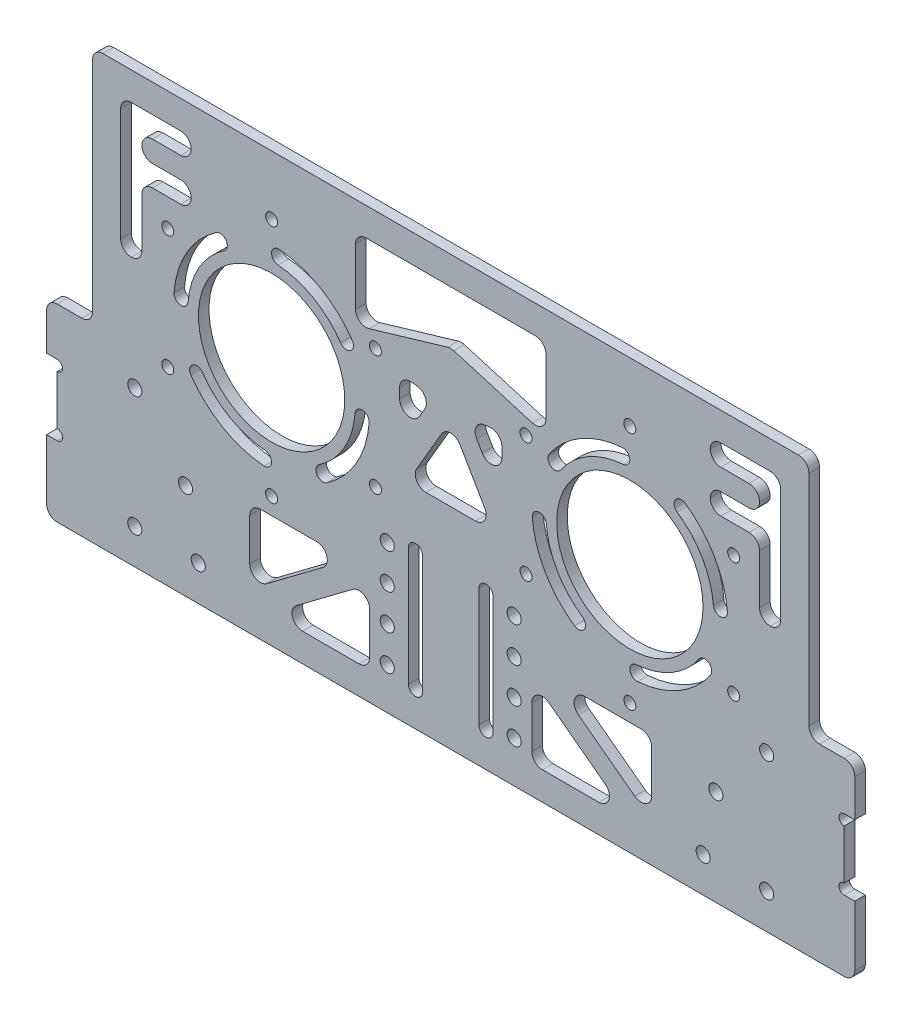
SolidWorks part; units mm, degrees
other "标注1"
sketch "草图3" plane through (101.6, -50.8, 0) normal (0.476, -0.0431, 0.8784) x (0.8786, 0.067, -0.4729)
ref_plane "前视基准面" through (0, 0, 0) normal (0, 0, 1) x (1, 0, 0)
ref_plane "上视基准面" through (0, 0, 0) normal (0, 1, 0) x (1, 0, 0)
ref_plane "右视基准面" through (0, 0, 0) normal (1, 0, 0) x (0, 0, -1)
sketch "草图1" plane through (0, 0, 0) normal (0, 0, 1) x (1, 0, 0)
  line L1 (-101.6, -60.8) -> (101.6, -60.8)
  line L2 (-101.6, -60.8) -> (-101.6, 60.8)
  line L3 (-101.6, 60.8) -> (101.6, 60.8)
  line L4 (101.6, -60.8) -> (101.6, 60.8)
  line L5 (-101.6, -60.8) -> (101.6, 60.8) construction
  line L6 (-101.6, 60.8) -> (101.6, -60.8) construction
  point P0 (0, 0)
  dimension "D1" = 121.6
  dimension "D2" = 203.2
extrude "凸台-拉伸1" add sketch "草图1" against normal blind 3
sketch "草图4" plane through (0, 0, 0) normal (0, 0, 1) x (1, 0, 0)
  line L0 (101.6, -40.8) -> (-101.6, -40.8) construction
  line L1 (101.6, -60.8) -> (101.6, 60.8) construction
  line L2 (-101.6, 60.8) -> (-101.6, -60.8) construction
  line L3 (-101.6, -60.8) -> (101.6, -60.8) construction
  line L4 (101.6, -40.8) -> (-101.6, 60.8) construction
  line L5 (-101.6, -40.8) -> (101.6, 60.8) construction
  line L6 (0, -40.8) -> (0, 60.8) construction
  line L7 (101.6, 60.8) -> (-101.6, 60.8) construction
  line L8 (0, -40.8) -> (101.6, 60.8) construction
  line L9 (0, 60.8) -> (101.6, -40.8) construction
  line L10 (0, 60.8) -> (-101.6, -40.8) construction
  line L11 (-101.6, 60.8) -> (0, -40.8) construction
  line L12 (-50.8, -40.8) -> (-50.8, 60.8) construction
  line L13 (101.6, 60.8) -> (-101.6, 60.8) construction
  line L14 (50.8, 60.8) -> (50.8, -40.8) construction
  point P20 (-50.8, 10)
  point P21 (50.8, 10)
  dimension "D1" = 20
sketch "草图5" plane through (0, 0, 0) normal (0, 0, 1) x (1, 0, 0)
  line L0 (0, 60.8) -> (-101.6, -40.8) construction
  line L1 (0, -40.8) -> (101.6, 60.8) construction
  line L2 (-50.8, 10) -> (-21.3551, 27) construction
  line L3 (50.8, 10) -> (50.8, 60.8) construction
  line L4 (-50.8, 10) -> (-50.8, 60.8) construction
  line L5 (101.6, 60.8) -> (-101.6, 60.8) construction
  line L6 (50.8, 10) -> (80.2449, 27) construction
  circle A0 centre (-50.8, 10) radius 20.75
  circle A1 centre (50.8, 10) radius 20.75
  circle A38 centre (-50.8, 10) radius 34.0001 construction
  circle A39 centre (-50.8, 44.0001) radius 1.7
  circle A40 centre (-21.3551, 27) radius 1.7
  circle A41 centre (-21.3551, -7) radius 1.7
  circle A42 centre (-50.8, -24.0001) radius 1.7
  circle A43 centre (-80.2449, -7) radius 1.7
  circle A44 centre (-80.2449, 27) radius 1.7
  circle A45 centre (50.8, 10) radius 34 construction
  circle A46 centre (50.8, 44) radius 1.7
  circle A47 centre (80.2449, 27) radius 1.7
  circle A48 centre (80.2449, -7) radius 1.7
  circle A49 centre (50.8, -24) radius 1.7
  circle A50 centre (21.3551, -7) radius 1.7
  circle A51 centre (21.3551, 27) radius 1.7
  point P27 (-50.8, 10)
  point P42 (50.8, 10)
  dimension "D1" = 41.5
  dimension "D2" = 41.5
  dimension "D4" = 6
  dimension "D3" = 3.4
  dimension "D5" = 60
  dimension "D6" = 34.0001
  dimension "D7" = 68
  dimension "D8" = 3.4
  dimension "D9" = 6
  dimension "D10" = 60
  dimension "D11" = 34
  dimension "D15" = 68.0002
extrude "切除-拉伸1" cut sketch "草图5" against normal up to next
sketch "草图6" plane through (-101.6, 0, 0) normal (-1, 0, 0) x (0, 0, 1)
  line L0 (0, -7.21) -> (-3, -7.21)
  line L4 (0, -60.8) -> (0, 60.8)
  line L5 (0, 60.8) -> (-3, 60.8)
  line L6 (-3, 60.8) -> (-3, -60.8)
  line L7 (-3, -60.8) -> (0, -60.8)
  line L8 (0, -60.8) -> (0, -7.21)
  line L10 (-3, -7.21) -> (-3, -60.8)
  line L11 (-3, -60.8) -> (0, -60.8)
  dimension "D2" = 53.59
  dimension "D1" = 0
extrude "凸台-拉伸2" add sketch "草图6" along normal blind 13
sketch "草图7" plane through (101.6, 0, 0) normal (1, 0, 0) x (0, 0, -1)
  line L0 (3, -7.21) -> (0, -7.21)
  line L4 (0, 60.8) -> (0, -60.8)
  line L5 (0, -60.8) -> (3, -60.8)
  line L6 (3, -60.8) -> (3, 60.8)
  line L7 (3, 60.8) -> (0, 60.8)
  line L8 (0, -7.21) -> (0, -60.8)
  line L9 (0, -60.8) -> (3, -60.8)
  line L10 (3, -60.8) -> (3, -7.21)
  dimension "D2" = 53.59
  dimension "D1" = 0
extrude "凸台-拉伸3" add sketch "草图7" along normal blind 13
fillet "圆角1" radius 3 4 edges at (101.6, -7.21, -1.5) (101.6, 60.8, -1.5) (-101.6, 60.8, -1.5) (-101.6, -7.21, -1.5)
sketch "草图9" plane through (0, 0, -3) normal (0, 0, -1) x (-1, 0, 0)
  line L0 (0, 19.8461) -> (12.2769, -1.2)
  line L1 (-12.2769, -1.2) -> (12.2769, -1.2)
  line L2 (-12.2769, -1.2) -> (0, 19.8461)
  line L3 (-27, 52.8) -> (27, 52.8)
  line L4 (-30, 55.8) -> (30, 55.8) construction
  line L5 (-30, 55.8) -> (-30, 25.8) construction
  line L6 (-30, 25.8) -> (-17.5, 25.8) construction
  line L7 (30, 55.8) -> (30, 25.8) construction
  line L8 (27, 52.8) -> (27, 29.8156)
  line L9 (-93.6, 14.8) -> (-93.6, 52.8)
  line L10 (-93.6, 52.8) -> (-73.6, 52.8)
  line L11 (0, 37.8) -> (27, 29.8156)
  line L12 (-27, 29.8156) -> (0, 37.8)
  line L13 (-27, 52.8) -> (-27, 29.8156)
  line L15 (-30, 25.8) -> (0, 34.6716) construction
  line L16 (38, -28.8) -> (54, -28.8)
  line L17 (57, -31.8) -> (57, -43.8)
  line L18 (52.2, -46.2) -> (36.2, -34.2)
  line L19 (23, -49.8) -> (23, -37.8)
  line L20 (27.8, -35.4) -> (43.8, -47.4)
  line L21 (42, -52.8) -> (26, -52.8)
  line L22 (12, -17.2102) -> (12, -50.8)
  line L23 (8, -50.8) -> (8, -17.2102)
  line L24 (-8, -17.2102) -> (-8, -50.8)
  line L25 (-12, -50.8) -> (-12, -17.2102)
  line L26 (-26, -52.8) -> (-42, -52.8)
  line L27 (-43.8, -47.4) -> (-27.8, -35.4)
  line L28 (-23, -37.8) -> (-23, -49.8)
  line L29 (-54, -28.8) -> (-38, -28.8)
  line L30 (-57, -43.8) -> (-57, -31.8)
  line L31 (-36.2, -34.2) -> (-52.2, -46.2)
  line L32 (0, -60.8) -> (0, 60.8) construction
  line L33 (114.6, -60.8) -> (-114.6, -60.8) construction
  line L34 (-98.6, 60.8) -> (98.6, 60.8) construction
  line L35 (0, 34.6716) -> (30, 25.8) construction
  line L36 (-17.5, -4.2) -> (17.5, -4.2) construction
  line L37 (-17.5, -4.2) -> (-17.5, 27.4557) construction
  line L38 (-17.5, 55.8) -> (17.5, 55.8) construction
  line L39 (17.5, -4.2) -> (17.5, 27.4557) construction
  line L40 (-17.5, -4.2) -> (0, 25.8) construction
  line L41 (0, 25.8) -> (17.5, -4.2) construction
  line L47 (0, 25.8) -> (-17.5, 27.4557) construction
  line L48 (17.5, 25.8) -> (30, 25.8) construction
  line L49 (17.5, 27.4557) -> (0, 25.8) construction
  line L50 (14.5, 6.8968) -> (14.5, 24.1585)
  line L51 (14.5, 24.1585) -> (4.9573, 23.2556)
  line L52 (4.9573, 23.2556) -> (14.5, 6.8968)
  line L53 (-4.9573, 23.2556) -> (-14.5, 24.1585)
  line L54 (-14.5, 6.8968) -> (-14.5, 24.1585)
  line L55 (-14.5, 6.8968) -> (-4.9573, 23.2556)
  line L60 (-73.6, 52.8) -> (-73.6, 46.8)
  line L61 (-73.6, 46.8) -> (-87.6, 46.8)
  line L62 (-87.6, 46.8) -> (-87.6, 40.8)
  line L63 (-87.6, 40.8) -> (-73.6, 40.8)
  line L64 (-73.6, 40.8) -> (-73.6, 34.8)
  line L65 (-73.6, 34.8) -> (-87.6, 34.8)
  line L66 (-87.6, 34.8) -> (-87.6, 14.8)
  line L67 (-87.6, 14.8) -> (-93.6, 14.8)
  line L68 (-101.6, -4.21) -> (-101.6, 57.8) construction
  line L69 (87.6, 14.8) -> (93.6, 14.8)
  line L70 (87.6, 34.8) -> (87.6, 14.8)
  line L71 (73.6, 34.8) -> (87.6, 34.8)
  line L72 (73.6, 40.8) -> (73.6, 34.8)
  line L73 (87.6, 40.8) -> (73.6, 40.8)
  line L74 (87.6, 46.8) -> (87.6, 40.8)
  line L75 (73.6, 46.8) -> (87.6, 46.8)
  line L76 (73.6, 52.8) -> (73.6, 46.8)
  line L77 (93.6, 52.8) -> (73.6, 52.8)
  line L78 (93.6, 14.8) -> (93.6, 52.8)
  line L79 (-50.8, 10) -> (-50.8, 37.75) construction
  line L82 (-50.8, 10) -> (-26.7678, 23.875) construction
  arc A0 (-37.3634, -9.5836) -> (-27.1217, 8.1553) centre (-50.8, 10) ccw
  arc A1 (-23.1338, 7.8447) -> (-27.1217, 8.1553) centre (-25.1278, 8) ccw
  circle A2 centre (-50.8, 10) radius 23.75
  arc A3 (-31.2164, 23.4366) -> (-48.9553, 33.6783) centre (-50.8, 10) ccw
  arc A4 (-35.1003, -12.8819) -> (-23.1338, 7.8447) centre (-50.8, 10) ccw
  arc A5 (73.6819, -5.6997) -> (70.3836, -3.4366) centre (72.0328, -4.5682) ccw
  arc A7 (-48.6447, 37.6662) -> (-48.9553, 33.6783) centre (-48.8, 35.6722) ccw
  circle A8 centre (-50.8, 10) radius 27.75
  arc A9 (-27.9181, 25.6997) -> (-48.6447, 37.6662) centre (-50.8, 10) ccw
  arc A10 (-27.9181, 25.6997) -> (-31.2164, 23.4366) centre (-29.5672, 24.5682) cw
  arc A11 (-35.1003, -12.8819) -> (-37.3634, -9.5836) centre (-36.2318, -11.2328) cw
  arc A12 (-70.3836, -3.4366) -> (-52.6447, -13.6783) centre (-50.8, 10) ccw
  arc A13 (-52.9553, -17.6662) -> (-52.6447, -13.6783) centre (-52.8, -15.6722) ccw
  arc A14 (-73.6819, -5.6997) -> (-52.9553, -17.6662) centre (-50.8, 10) ccw
  arc A15 (-73.6819, -5.6997) -> (-70.3836, -3.4366) centre (-72.0328, -4.5682) cw
  arc A16 (-64.2366, 29.5836) -> (-74.4783, 11.8447) centre (-50.8, 10) ccw
  arc A17 (-78.4662, 12.1553) -> (-74.4783, 11.8447) centre (-76.4722, 12) ccw
  arc A18 (-66.4997, 32.8819) -> (-78.4662, 12.1553) centre (-50.8, 10) ccw
  arc A19 (-66.4997, 32.8819) -> (-64.2366, 29.5836) centre (-65.3682, 31.2328) cw
  arc A21 (73.6819, -5.6997) -> (52.9553, -17.6662) centre (50.8, 10) cw
  arc A22 (52.9553, -17.6662) -> (52.6447, -13.6783) centre (52.8, -15.6722) cw
  arc A23 (70.3836, -3.4366) -> (52.6447, -13.6783) centre (50.8, 10) cw
  arc A24 (35.1003, -12.8819) -> (37.3634, -9.5836) centre (36.2318, -11.2328) ccw
  arc A25 (35.1003, -12.8819) -> (23.1338, 7.8447) centre (50.8, 10) cw
  arc A26 (23.1338, 7.8447) -> (27.1217, 8.1553) centre (25.1278, 8) cw
  arc A27 (37.3634, -9.5836) -> (27.1217, 8.1553) centre (50.8, 10) cw
  circle A28 centre (71.6, -50.8) radius 2
  circle A29 centre (75.1892, -33.6216) radius 2
  circle A30 centre (89.6, -16.8) radius 2
  arc A31 (52.2, -46.2) -> (57, -43.8) centre (54, -43.8) ccw
  arc A32 (38, -28.8) -> (36.2, -34.2) centre (38, -31.8) ccw
  arc A33 (27.8, -35.4) -> (23, -37.8) centre (26, -37.8) ccw
  arc A34 (23, -49.8) -> (26, -52.8) centre (26, -49.8) ccw
  arc A35 (42, -52.8) -> (43.8, -47.4) centre (42, -49.8) ccw
  circle A36 centre (18, -19.0051) radius 2
  circle A37 centre (18, -29.0051) radius 2
  circle A38 centre (18, -39.0051) radius 2
  circle A39 centre (18, -49.0051) radius 2
  arc A40 (8, -50.8) -> (12, -50.8) centre (10, -50.8) ccw
  arc A41 (12, -17.2102) -> (8, -17.2102) centre (10, -17.2102) ccw
  arc A42 (-12, -50.8) -> (-8, -50.8) centre (-10, -50.8) ccw
  arc A43 (-8, -17.2102) -> (-12, -17.2102) centre (-10, -17.2102) ccw
  circle A44 centre (-18, -49.0051) radius 2
  circle A45 centre (-18, -39.0051) radius 2
  circle A46 centre (-18, -19.0051) radius 2
  circle A47 centre (-18, -29.0051) radius 2
  arc A48 (-23, -37.8) -> (-27.8, -35.4) centre (-26, -37.8) ccw
  arc A49 (-43.8, -47.4) -> (-42, -52.8) centre (-42, -49.8) ccw
  arc A50 (-36.2, -34.2) -> (-38, -28.8) centre (-38, -31.8) ccw
  arc A51 (-54, -28.8) -> (-57, -31.8) centre (-54, -31.8) ccw
  arc A52 (-57, -43.8) -> (-52.2, -46.2) centre (-54, -43.8) ccw
  circle A53 centre (-71.6, -50.8) radius 2
  circle A54 centre (-75.1892, -33.6216) radius 2
  circle A55 centre (-89.6, -16.8) radius 2
  arc A56 (27.9181, 25.6997) -> (31.2164, 23.4366) centre (29.5672, 24.5682) ccw
  arc A57 (57, -31.8) -> (54, -28.8) centre (54, -31.8) ccw
  arc A58 (27.9181, 25.6997) -> (48.6447, 37.6662) centre (50.8, 10) cw
  arc A59 (-26, -52.8) -> (-23, -49.8) centre (-26, -49.8) ccw
  arc A60 (48.6447, 37.6662) -> (48.9553, 33.6783) centre (48.8, 35.6722) cw
  arc A61 (31.2164, 23.4366) -> (48.9553, 33.6783) centre (50.8, 10) cw
  arc A62 (66.4997, 32.8819) -> (64.2366, 29.5836) centre (65.3682, 31.2328) ccw
  arc A63 (66.4997, 32.8819) -> (78.4662, 12.1553) centre (50.8, 10) cw
  arc A64 (78.4662, 12.1553) -> (74.4783, 11.8447) centre (76.4722, 12) cw
  arc A65 (64.2366, 29.5836) -> (74.4783, 11.8447) centre (50.8, 10) cw
  circle A67 centre (-89.6, -50.8) radius 2
  circle A69 centre (89.6, -50.8) radius 2
  point P60 (0, 25.8)
  point P79 (0, 29.7738)
  point P104 (-14.5, 6.8968)
  point P105 (-14.5, 30.1959)
  point P107 (14.5, 30.1959)
  point P108 (14.5, 6.8968)
  point P109 (0, 31.7539)
  point P112 (0, 52.8)
  point P176 (-50.8, 10)
  dimension "D21" = 60
  dimension "D22" = 4
  dimension "D1" = 35
  dimension "D2" = 60
  dimension "D3" = 35
  dimension "D5" = 30
  dimension "D6" = 60
  dimension "D8" = 15
  dimension "D9" = 3
  dimension "D11" = 8
  dimension "D12" = 6
  dimension "D13" = 8
  dimension "D14" = 6
  dimension "D15" = 6
  dimension "D16" = 20
  dimension "D17" = 20
  dimension "D4" = 3
  dimension "D7" = 3
  dimension "D10" = 3
  dimension "D18" = 3
  dimension "D20" = 7
extrude "切除-拉伸2" cut sketch "草图9" against normal through all
fillet "圆角2" radius 3 34 edges at (-14.5, 6.8968, -1.5) (-4.9573, 23.2556, -1.5) (-14.5, 24.1585, -1.5) (4.9573, 23.2556, -1.5) (14.5, 24.1585, -1.5) (14.5, 6.8968, -1.5) (12.2769, -1.2, -1.5) (-12.2769, -1.2, -1.5) (-93.6, 14.8, -1.5) (-87.6, 14.8, -1.5) (-73.6, 40.8, -1.5) (-87.6, 34.8, -1.5) (-73.6, 34.8, -1.5) (-87.6, 40.8, -1.5) (-87.6, 46.8, -1.5) (-73.6, 46.8, -1.5) (-73.6, 52.8, -1.5) (-93.6, 52.8, -1.5) (-27, 52.8, -1.5) (-27, 29.8156, -1.5) (0, 37.8, -1.5) (27, 29.8156, -1.5) (27, 52.8, -1.5) (93.6, 52.8, -1.5) (87.6, 46.8, -1.5) (73.6, 46.8, -1.5) (73.6, 52.8, -1.5) (73.6, 40.8, -1.5) (73.6, 34.8, -1.5) (87.6, 40.8, -1.5) (87.6, 34.8, -1.5) (87.6, 14.8, -1.5) (93.6, 14.8, -1.5) (0, 19.8461, -1.5)
sketch "草图10" plane through (0, 0, 0) normal (0, 0, 1) x (1, 0, 0)
  line L0 (-114.6, -60.8) -> (-114.6, -7.21) construction
  line L1 (-114.6, -20.8) -> (-111.6, -20.8)
  line L2 (-114.6, -20.8) -> (-114.6, -40.8)
  line L3 (-114.6, -40.8) -> (-111.6, -40.8)
  line L4 (-111.6, -23.8) -> (-111.6, -37.8)
  line L5 (-114.6, -60.8) -> (114.6, -60.8) construction
  line L11 (0, -1.65) -> (0, 1.65) construction
  line L12 (114.6, -20.8) -> (114.6, -40.8)
  line L13 (114.6, -40.8) -> (111.6, -40.8)
  line L14 (111.6, -23.8) -> (111.6, -37.8)
  line L15 (114.6, -20.8) -> (111.6, -20.8)
  arc A0 (-111.6, -23.8) -> (-111.6, -20.8) centre (-111.6, -22.3) ccw
  arc A1 (-111.6, -40.8) -> (-111.6, -37.8) centre (-111.6, -39.3) ccw
  arc A2 (111.6, -40.8) -> (111.6, -37.8) centre (111.6, -39.3) cw
  arc A3 (111.6, -23.8) -> (111.6, -20.8) centre (111.6, -22.3) cw
  dimension "D4" = 3
  dimension "D5" = 3
  dimension "D1" = 3
  dimension "D2" = 20
  dimension "D3" = 20
extrude "切除-拉伸3" cut sketch "草图10" against normal through all
fillet "圆角3" radius 3 4 edges at (114.6, -7.21, -1.5) (114.6, -60.8, -1.5) (-114.6, -60.8, -1.5) (-114.6, -7.21, -1.5)
